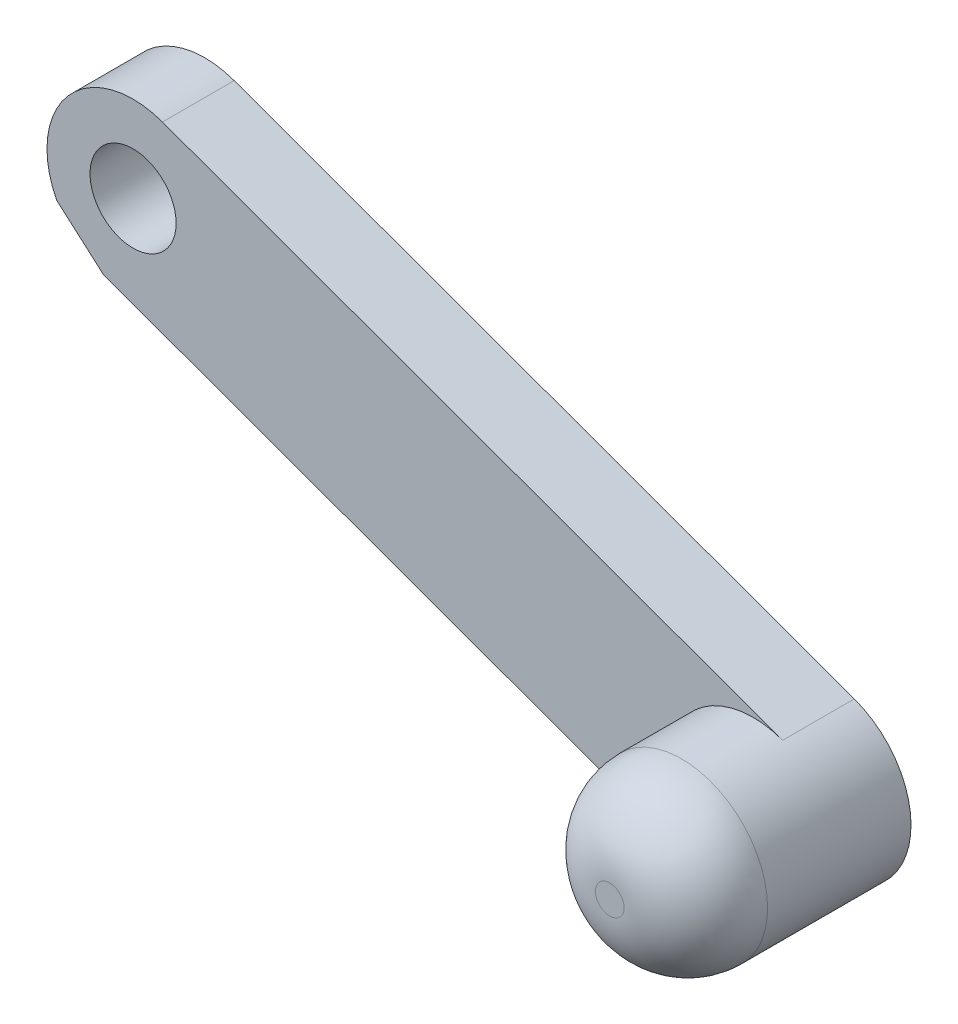
SolidWorks part; units mm, degrees
ref_plane "Alzado" through (0, 0, 0) normal (0, 0, 1) x (1, 0, 0)
ref_plane "Planta" through (0, 0, 0) normal (0, 1, 0) x (1, 0, 0)
ref_plane "Vista lateral" through (0, 0, 0) normal (1, 0, 0) x (0, 0, -1)
sketch "Croquis1" plane through (0, 0, -107.5) normal (0, 0, 1) x (1, 0, 0)
  line L0 (153.0518, -38.5646) -> (174.6689, -46.4197) construction
  line L1 (152.0272, -41.3842) -> (173.6443, -49.2393)
  line L2 (154.0764, -35.745) -> (175.6934, -43.6)
  circle A2 centre (153.0518, -38.5646) radius 3
  circle A3 centre (153.0518, -38.5646) radius 1.5
  circle A4 centre (174.6689, -46.4197) radius 0.9015
  circle A6 centre (174.6689, -46.4197) radius 3
  line M2 (147.1506, -37.1101) -> (156.8415, -45.61)
  arc M6 (162.9572, -39.9368) -> (158.532, -30.2) centre (153.0518, -38.5646) ccw
  circle M9 centre (153.0518, -38.5646) radius 1.5
  dimension "D1" = 3
  dimension "D2" = 3
extrude "Saliente-Extruir1" add sketch "Croquis1" along normal blind 2.5 contours A6 A4 | L0 L1 A6 M6 | L0 A2 L1 M6 | A2 L0 L2 M6 | L0 A6 L2 M6 | A2 M9 M2 region at (163.8603, -42.4921, -107.5) region at (152.0532, -41.3034, -107.5) region at (171.929, -45.4241, -107.5)
sketch "Croquis2" plane through (0, 0, -105) normal (0, 0, 1) x (1, 0, 0)
  circle A0 centre (174.6689, -46.4197) radius 3
extrude "Saliente-Extruir2" add sketch "Croquis2" along normal blind 5
fillet "Redondeo1" radius 2.5 1 edges at (177.6689, -46.4197, -100)
